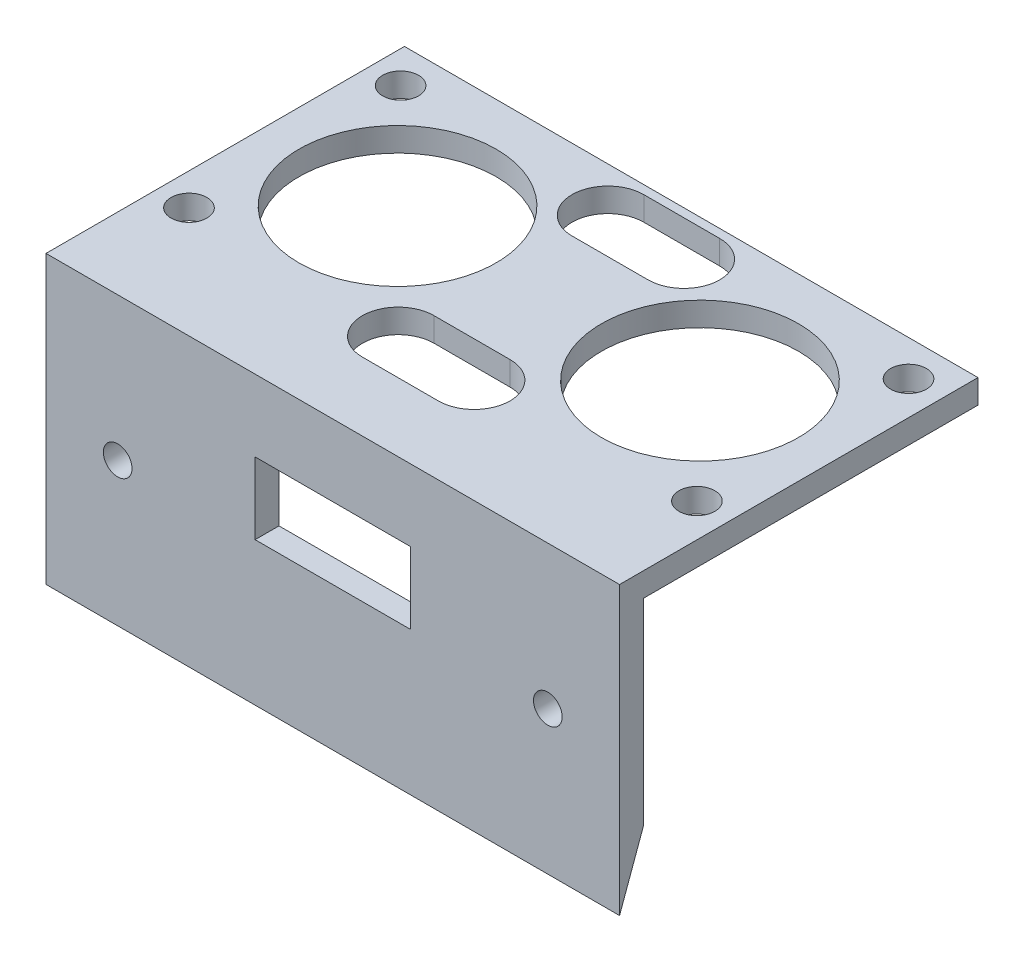
SolidWorks part; units mm, degrees
ref_plane "Ebene vorne" through (0, 0, 0) normal (0, 0, 1) x (1, 0, 0)
ref_plane "Ebene oben" through (0, 0, 0) normal (0, 1, 0) x (1, 0, 0)
ref_plane "Ebene rechts" through (0, 0, 0) normal (1, 0, 0) x (0, 0, -1)
ref_plane "Ebene1" through (0, 23.2667, 0) normal (0, 1, 0) x (1, 0, 0)
sketch "Skizze1" plane through (0, 23.2667, 0) normal (0, 1, 0) x (1, 0, 0)
  line L0 (-5.8403, -23.3194) -> (42.1597, -23.3194) construction
  line L1 (21.2712, -29.0944) -> (14.9112, -29.0944)
  line L2 (14.9112, -11.5444) -> (21.2712, -11.5444)
  line L3 (21.2712, -17.5444) -> (14.9112, -17.5444)
  line L4 (-5.8403, -10.8194) -> (-5.8403, -35.8194)
  line L5 (14.9112, -35.0944) -> (21.2712, -35.0944)
  line L10 (42.1597, -35.8194) -> (42.1597, -10.8194)
  line L11 (42.1597, -10.8194) -> (-5.8403, -10.8194)
  line L12 (-5.8403, -35.8194) -> (42.1597, -35.8194)
  arc A0 (21.2712, -35.0944) -> (21.2712, -29.0944) centre (21.2712, -32.0944) ccw
  arc A1 (14.9112, -29.0944) -> (14.9112, -35.0944) centre (14.9112, -32.0944) ccw
  circle A2 centre (5.4362, -22.6744) radius 8.25
  arc A3 (21.2712, -11.5444) -> (21.2712, -17.5444) centre (21.2712, -14.5444) cw
  arc A4 (14.9112, -17.5444) -> (14.9112, -11.5444) centre (14.9112, -14.5444) cw
  circle A5 centre (30.7462, -22.6744) radius 8.25
  circle A6 centre (39.3462, -31.5294) radius 1.5
  circle A7 centre (39.3462, -13.8194) radius 1.5
  circle A8 centre (-3.1638, -13.8194) radius 1.5
  circle A9 centre (-3.1638, -31.5294) radius 1.5
  dimension "D1" = 25
  dimension "D2" = 3
extrude "Aufsatz-Linear austragen1" add sketch "Skizze1" against normal blind 2
ref_plane "Skizzierebene" through (0, 21.2667, 0) normal (0, -1, 0) x (-1, 0, 0)
sketch "Skizze2" plane through (0, 21.2667, 0) normal (0, -1, 0) x (-1, 0, 0)
  line L1 (-42.1597, -35.8194) -> (5.8403, -35.8194)
  line L2 (-42.1597, -35.8194) -> (-42.1597, -40.8194)
  line L3 (-42.1597, -40.8194) -> (5.8403, -40.8194)
  line L4 (5.8403, -35.8194) -> (5.8403, -40.8194)
  dimension "D1" = 5
extrude "Aufsatz-Linear austragen2" add sketch "Skizze2" against normal up to surface (2 mm away) up to face at (-3.1638, 23.2667, 30.0294)
ref_plane "Ebene3" through (0, 0, 40.8194) normal (0, 0, 1) x (1, 0, 0)
sketch "Skizze3" plane through (0, 0, 40.8194) normal (0, 0, 1) x (1, 0, 0)
  line L0 (-25.0036, 21.2667) -> (25.0036, 21.2667) construction
  line L1 (42.1597, 21.2667) -> (-5.8403, 21.2667)
  line L2 (42.1597, 21.2667) -> (42.1597, -0.7333)
  line L3 (42.1597, -0.7333) -> (-5.8403, -0.7333)
  line L4 (-5.8403, 21.2667) -> (-5.8403, -0.7333)
  point P6 (-5.8403, 21.2667)
  point P8 (42.1597, 21.2667)
  dimension "D1" = 22
extrude "Aufsatz-Linear austragen3" add sketch "Skizze3" against normal blind 2
ref_plane "Ebene4" through (32.1597, 0, 0) normal (1, 0, 0) x (0, 0, -1)
ref_plane "Spiegelebene" through (18.1597, 0, 0) normal (1, 0, 0) x (0, 0, -1)
sketch "Skizze5" plane through (32.1597, 0, 0) normal (1, 0, 0) x (0, 0, -1)
  line L0 (-38.8194, 17.2667) -> (-38.8194, 21.2667)
  line L1 (-38.8194, -0.7333) -> (-38.8194, 21.2667) construction
  line L2 (-25.0036, 21.2667) -> (25.0036, 21.2667) construction
  line L3 (-38.8194, 21.2667) -> (-34.8194, 21.2667)
  line L4 (-34.8194, 21.2667) -> (-38.8194, 17.2667)
  dimension "D1" = 4
  dimension "D2" = 4
extrude "Aufsatz-Linear austragen4" add sketch "Skizze5" along normal blind 1.5 and the other way blind 1.5
mirror "Spiegeln1" about plane through (18.1597, 0, 0) normal (1, 0, 0) of "Aufsatz-Linear austragen4"
sketch "Skizze6" plane through (0, 0, 38.8194) normal (0, 0, -1) x (-1, 0, 0)
  line L0 (-18.1597, 12.1) -> (-18.1597, -12.1) construction
  line L10 (-25.0036, 21.2667) -> (25.0036, 21.2667) construction
  line L11 (-24.6597, 11.2667) -> (-11.6597, 11.2667)
  line L15 (-24.6597, 11.2667) -> (-24.6597, 17.2667)
  line L16 (-24.6597, 17.2667) -> (-11.6597, 17.2667)
  line L17 (-11.6597, 11.2667) -> (-11.6597, 17.2667)
  line L18 (-24.6597, 11.2667) -> (-11.6597, 17.2667) construction
  line L19 (-24.6597, 17.2667) -> (-11.6597, 11.2667) construction
  point P0 (-18.1597, 13.6426)
  point P4 (-18.1597, 14.2667)
  dimension "D1" = 13
  dimension "D2" = 4
  dimension "D3" = 10
extrude "Schnitt-Linear austragen1" cut sketch "Skizze6" against normal through all both and the other way through all
sketch "Skizze7" plane through (0, 0, 38.8194) normal (0, 0, -1) x (-1, 0, 0)
  line L0 (-42.1597, 21.2667) -> (5.8403, 21.2667) construction
  line L1 (-42.1597, -0.7333) -> (-42.1597, 21.2667) construction
  line L3 (-18.1597, 12.1) -> (-18.1597, -12.1) construction
  circle A0 centre (-36.1597, 11.2667) radius 1.2
  circle A1 centre (-0.1597, 11.2667) radius 1.2
  dimension "D1" = 2.4
  dimension "D2" = 6
  dimension "D3" = 10
extrude "Schnitt-Linear austragen2" cut sketch "Skizze7" against normal through all both
chamfer "Fase1" distance 5.5 angle 20 1 edges at (18.1597, -0.7333, 38.8194) first distance on face at (34.9597, 11.2667, 38.8194)
